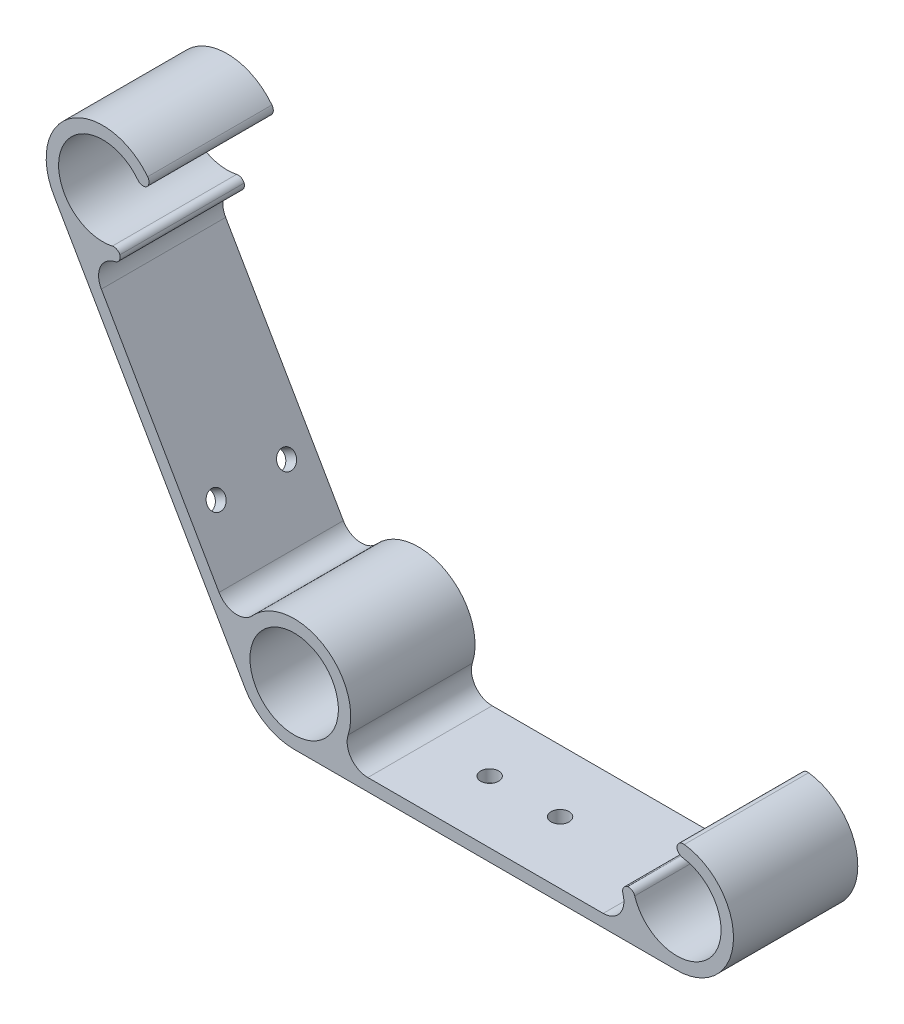
SolidWorks part; units mm, degrees
ref_plane "Front Plane" through (0, 0, 0) normal (0, 0, 1) x (1, 0, 0)
ref_plane "Top Plane" through (0, 0, 0) normal (0, 1, 0) x (1, 0, 0)
ref_plane "Right Plane" through (0, 0, 0) normal (1, 0, 0) x (0, 0, -1)
sketch "Sketch3" plane through (0, 0, 0) normal (0, 1, 0) x (1, 0, 0)
  line L1 (-57.15, -19.05) -> (57.15, -19.05)
  line L2 (-57.15, -19.05) -> (-57.15, 19.05)
  line L3 (-57.15, 19.05) -> (57.15, 19.05)
  line L4 (57.15, -19.05) -> (57.15, 19.05)
  line L5 (-57.15, -19.05) -> (57.15, 19.05) construction
  line L6 (-57.15, 19.05) -> (57.15, -19.05) construction
  point P0 (0, 0)
  dimension "D1" = 38.1
  dimension "D2" = 114.3
extrude "Boss-Extrude1" add sketch "Sketch3" along normal blind 3.81
sketch "Sketch4" plane through (0, 0, 0) normal (0, 0, 1) x (1, 0, 0)
  line L0 (-58.6588, 17.3553) -> (58.6588, 17.3553) construction
  line L1 (57.15, 3.81) -> (-57.15, 3.81) construction
  line L2 (0, -2.0955) -> (0, 2.0955) construction
  line L5 (20.955, 0) -> (-20.955, 0) construction
  line L8 (-57.15, 3.81) -> (57.15, 3.81) construction
  line L9 (-36.0719, 3.81) -> (36.0719, 3.81)
  line L11 (-57.15, 0) -> (57.15, 0) construction
  line L12 (74.7593, 0) -> (-74.7593, 0) construction
  line L13 (0, 3.81) -> (0, 0)
  line L14 (58.6588, 0) -> (-58.6588, 0)
  line L15 (-58.6588, 17.3553) -> (-24.1786, 77.0768) construction
  line L16 (58.6588, 17.3553) -> (41.5671, 14.3416) construction
  line L17 (58.6588, 17.3553) -> (58.6588, 34.7106) construction
  line L18 (58.6588, 17.3553) -> (64.5947, 33.664) construction
  line L19 (41.5671, 14.3416) -> (45.3193, 15.0032)
  line L20 (58.6588, 34.7106) -> (58.6588, 30.9006)
  line L21 (-132.3477, 110.2777) -> (-73.6889, 8.6777)
  line L22 (-81.6828, 30.1435) -> (-117.7547, 92.6218)
  line L23 (-111.3817, 102.6467) -> (-112.6848, 106.2269)
  line L24 (-102.2874, 127.633) -> (-105.587, 125.728)
  circle A0 centre (-58.6588, 17.3553) radius 13.5453
  arc A1 (45.3193, 15.0032) -> (63.2916, 30.0837) centre (58.6588, 17.3553) ccw
  arc A2 (-42.1223, 12.0874) -> (-76.0141, 17.3553) centre (-58.6588, 17.3553) ccw
  arc A3 (42.1223, 12.0874) -> (41.5671, 14.3416) centre (58.6588, 17.3553) cw
  arc A4 (-36.0719, 3.81) -> (-42.1223, 12.0874) centre (-36.0719, 10.16) cw
  arc A5 (36.0719, 3.81) -> (42.1223, 12.0874) centre (36.0719, 10.16) ccw
  arc A6 (42.1223, 12.0874) -> (41.5671, 14.3416) centre (58.6588, 17.3553) cw
  arc A7 (-42.1223, 12.0874) -> (-76.0141, 17.3553) centre (-58.6588, 17.3553) ccw
  arc A8 (41.5671, 14.3416) -> (42.1223, 12.0874) centre (58.6588, 17.3553) ccw
  arc A9 (64.5947, 33.664) -> (76.0141, 17.3553) centre (58.6588, 17.3553) cw
  arc A10 (64.5947, 33.664) -> (76.0141, 17.3553) centre (58.6588, 17.3553) cw
  arc A11 (58.6588, 0) -> (64.5947, 33.664) centre (58.6588, 17.3553) ccw
  arc A12 (63.2916, 30.0837) -> (58.6588, 30.9006) centre (58.6588, 17.3553) ccw
  arc A13 (64.5947, 33.664) -> (58.6588, 34.7106) centre (58.6588, 17.3553) ccw
  arc A15 (-76.0141, 17.3553) -> (-58.6588, 0) centre (-58.6588, 17.3553) ccw
  arc A16 (-132.3477, 110.2777) -> (-106.1618, 132.2503) centre (-117.3176, 118.9553) cw
  arc A17 (-113.6114, 102.0003) -> (-111.3817, 102.6467) centre (-117.3176, 118.9553) ccw
  arc A18 (-106.1618, 132.2503) -> (-102.2874, 127.633) centre (-117.3176, 118.9553) cw
  arc A19 (-108.6108, 129.3316) -> (-105.587, 125.728) centre (-117.3176, 118.9553) cw
  arc A20 (-106.1618, 132.2503) -> (-125.9952, 133.9855) centre (-117.3176, 118.9553) ccw
  arc A21 (-112.6848, 106.2269) -> (-108.6108, 129.3316) centre (-117.3176, 118.9553) cw
  arc A22 (-117.7547, 92.6218) -> (-113.6114, 102.0003) centre (-112.2554, 95.7968) cw
  arc A23 (-49.9811, 2.3252) -> (-73.6889, 8.6777) centre (-58.6588, 17.3553) cw
  arc A24 (-81.6828, 30.1435) -> (-71.4892, 29.0424) centre (-76.1836, 33.3185) ccw
  arc A25 (-71.4892, 29.0424) -> (-49.9811, 2.3252) centre (-58.6588, 17.3553) cw
  point P6 (0, 17.3553)
  point P28 (-47.8084, 3.81)
  dimension "D1" = 27.0906
  dimension "D4" = 3.81
  dimension "D5" = 6.35
  dimension "D2" = 117.3176
  dimension "D3" = 60
  dimension "D6" = 100
  dimension "D7" = 20
sketch "Sketch5" plane through (0, 3.81, 0) normal (0, 1, 0) x (1, 0, 0)
  line L0 (0, -2.0955) -> (0, 2.0955) construction
  line L1 (57.15, 19.05) -> (-57.15, 19.05) construction
  line L2 (0, 13.545) -> (0, 19.05) construction
  line L3 (-2.0955, 0) -> (2.0955, 0) construction
  line L4 (0, -13.545) -> (0, -19.05) construction
  line L5 (-17.78, 19.05) -> (-17.78, -19.05) construction
  line L6 (-57.15, -19.05) -> (57.15, -19.05) construction
  circle A0 centre (0, 10.795) radius 2.75 construction
  circle A1 centre (0, -10.795) radius 2.75 construction
  circle A2 centre (-17.78, 10.795) radius 2.75 construction
  circle A3 centre (-17.78, -10.795) radius 2.75 construction
  circle A4 centre (-17.78, 0) radius 2.75
  circle A5 centre (3.81, 0) radius 2.75
  dimension "D2" = 5.5
  dimension "D1" = 21.59
  dimension "D4" = 21.59
  dimension "D3" = 17.78
extrude "Boss-Extrude2" add sketch "Sketch4" along normal mid plane 38.1 contours A0 A2 L12 L13 L9 A4 | A5 L9 L13 L12 A6 A1 A3 | A25 A2 A7 A15 A23 A0 | A24 L22 A22 A17 L23 A21 A19 L24 A18 A16 L21 A15 A7 region at (-27.6447, 2.2944, 0) region at (46.8476, 8.7031, 0) region at (-45.5221, 6.78, 0) region at (-76.1715, 24.1358, 0)
fillet "Fillet1" radius 2.032 8 edges at (58.6588, 34.7106, 0) (58.6588, 30.9006, 0) (45.3193, 15.0032, 0) (41.5671, 14.3416, 0) (-102.2874, 127.633, 0) (-105.587, 125.728, 0) (-112.6848, 106.2269, 0) (-111.3817, 102.6467, 0)
extrude "Cut-Extrude4" cut sketch "Sketch5" against normal blind 12.7
sketch "Sketch6" plane through (-48.2096, -27.8338, 0) normal (0.866, 0.5, 0) x (0, 0, -1)
  line L0 (-19.05, 103.0183) -> (19.05, 103.0183) construction
  line L1 (-19.05, 66.9465) -> (-19.05, 139.0902) construction
  line L2 (19.05, 66.9465) -> (19.05, 139.0902) construction
  line L3 (-19.05, 85.2383) -> (19.05, 85.2383) construction
  line L4 (0, 74.9708) -> (0, -74.9708) construction
  circle A0 centre (-10.795, 85.2383) radius 2.75
  circle A1 centre (10.795, 85.2383) radius 2.75
  dimension "D1" = 5.5
  dimension "D2" = 21.59
  dimension "D3" = 17.78
extrude "Cut-Extrude5" cut sketch "Sketch6" against normal blind 7.62
